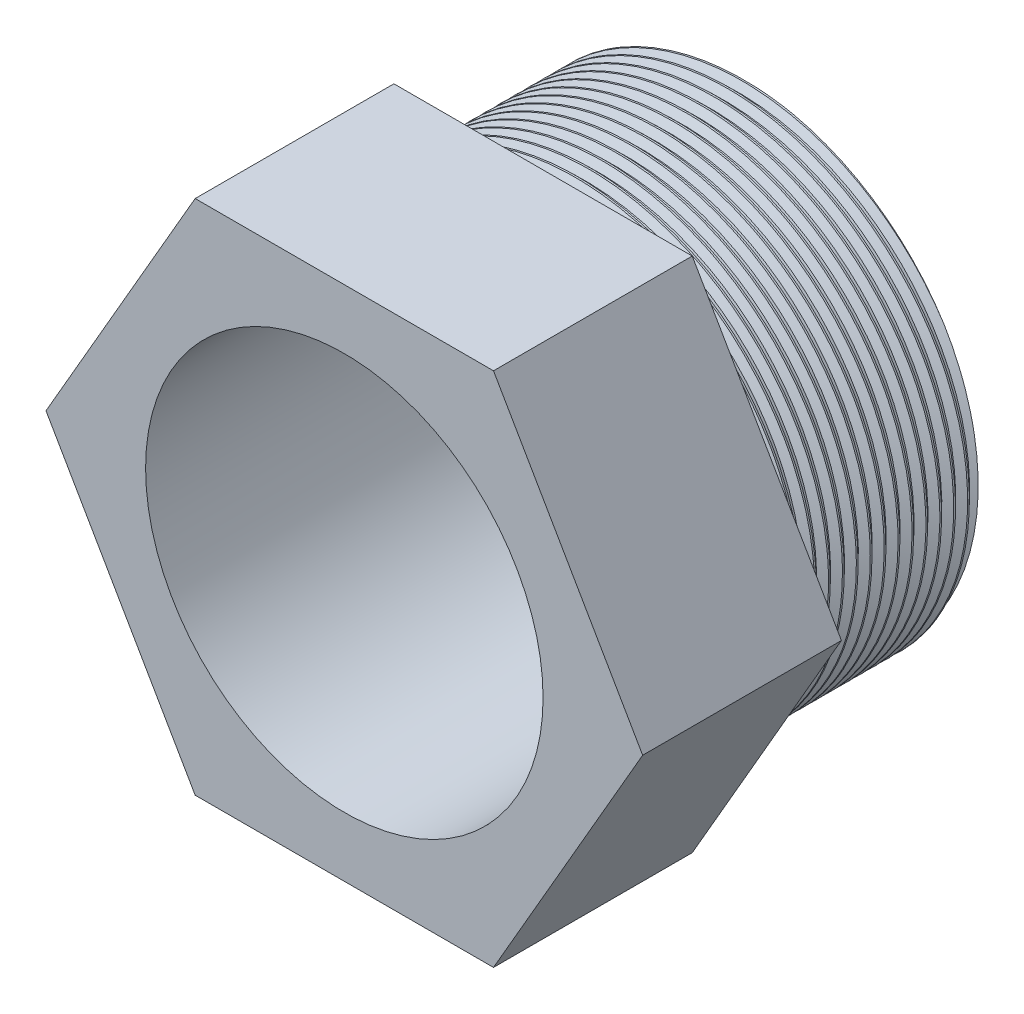
SolidWorks part; units mm, degrees
ref_plane "Front Plane" through (0, 0, 0) normal (0, 0, 1) x (1, 0, 0)
ref_plane "Top Plane" through (0, 0, 0) normal (0, 1, 0) x (1, 0, 0)
ref_plane "Right Plane" through (0, 0, 0) normal (1, 0, 0) x (0, 0, -1)
sketch "Sketch1" plane through (0, 0, 0) normal (0, 0, 1) x (1, 0, 0)
  line L1 (3.7528, -6.5) -> (7.5056, 0)
  line L2 (7.5056, 0) -> (3.7528, 6.5)
  line L3 (3.7528, 6.5) -> (-3.7528, 6.5)
  line L4 (-3.7528, 6.5) -> (-7.5056, 0)
  line L5 (-7.5056, 0) -> (-3.7528, -6.5)
  line L6 (-3.7528, -6.5) -> (3.7528, -6.5)
  circle A0 centre (0, 0) radius 5
  circle A1 centre (0, 0) radius 6.5 construction
  circle A2 centre (0, 0) radius 6
  point P3 (0, 6.5)
  dimension "D1" = 10
  dimension "D2" = 13
  dimension "D3" = 12
extrude "Boss-Extrude1" add sketch "Sketch1" along normal blind 5 contours A2 A0 | L5 L6 L1 L2 L3 L4 A2 region at (0, -6.3014, 0) region at (-5.8303, 0, 0)
extrude "Boss-Extrude2" add sketch "Sketch1<3>" against normal blind 5 contours A2 A0 region at (-5.8303, 0, 0)
sketch "Sketch1<3>" plane through (0, 0, 0) normal (0, 0, 1) x (1, 0, 0) same geometry as "Sketch1"
thread "Thread1" pitch 0.35 method cut profile "Thread Profile1" start angle 0, offset 0, length 0, pitch 0.35, diameter 12
ref_plane "Plane1" through (-6, 0, 0) normal (0, -1, 0) x (-1, 0, 0)
sketch "Thread Profile1" plane through (-6, 0, 0) normal (0, -1, 0) x (-1, 0, 0)
  line L0 (0, 0) -> (0, 0.35) construction
  line L11 (0, 0) -> (0, 0.3062)
  line L12 (0, 0.3062) -> (-0.1894, 0.1969)
  line L13 (-0.1894, 0.1969) -> (-0.1894, 0.1094)
  line L15 (-0.1894, 0.1094) -> (0, 0)
  line L17 (-0.1894, 0.1531) -> (0, 0.1531) construction
  point P2 (0, 0)
  dimension "Pitch" = 0.35
  dimension "Profile_Angle" = 60
  dimension "Profile_Land" = 0.0875
  dimension "Profile_Height" = 0.1894
